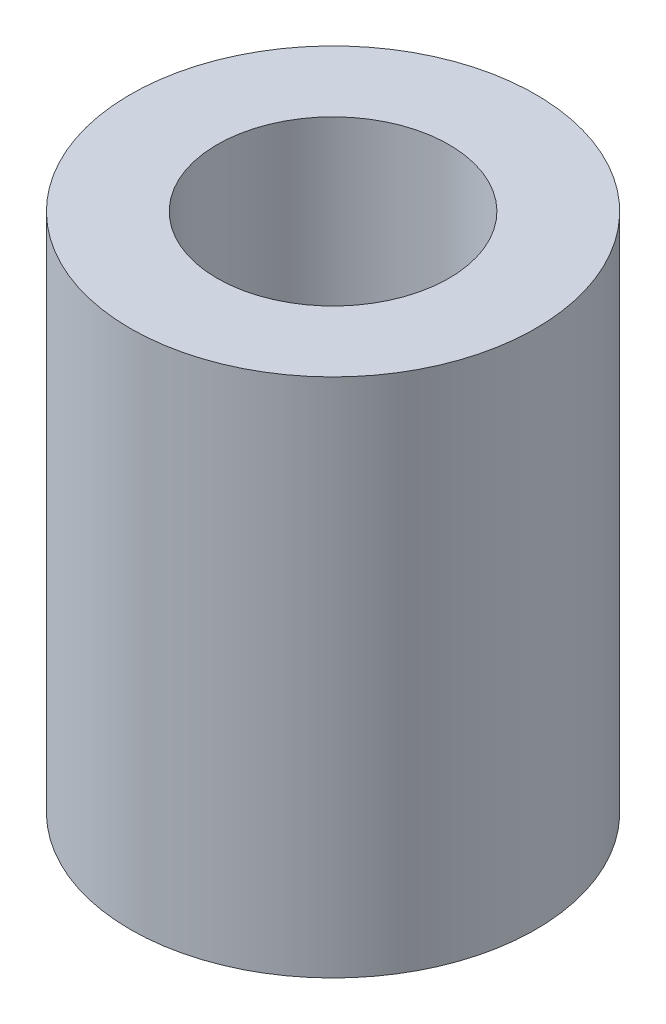
SolidWorks part; units mm, degrees
ref_plane "Front" through (0, 0, 0) normal (0, 0, 1) x (1, 0, 0)
ref_plane "Top" through (0, 0, 0) normal (0, 1, 0) x (1, 0, 0)
ref_plane "Right" through (0, 0, 0) normal (1, 0, 0) x (0, 0, -1)
sketch "Sketch2" plane through (0, 0, 0) normal (0, 1, 0) x (1, 0, 0)
  circle A0 centre (0, 0) radius 5.335
  circle A1 centre (0, 0) radius 3.05
  dimension "D1" = 10.67
  dimension "D2" = 6.1
extrude "Boss-Extrude1" add sketch "Sketch2" along normal blind 13.7
